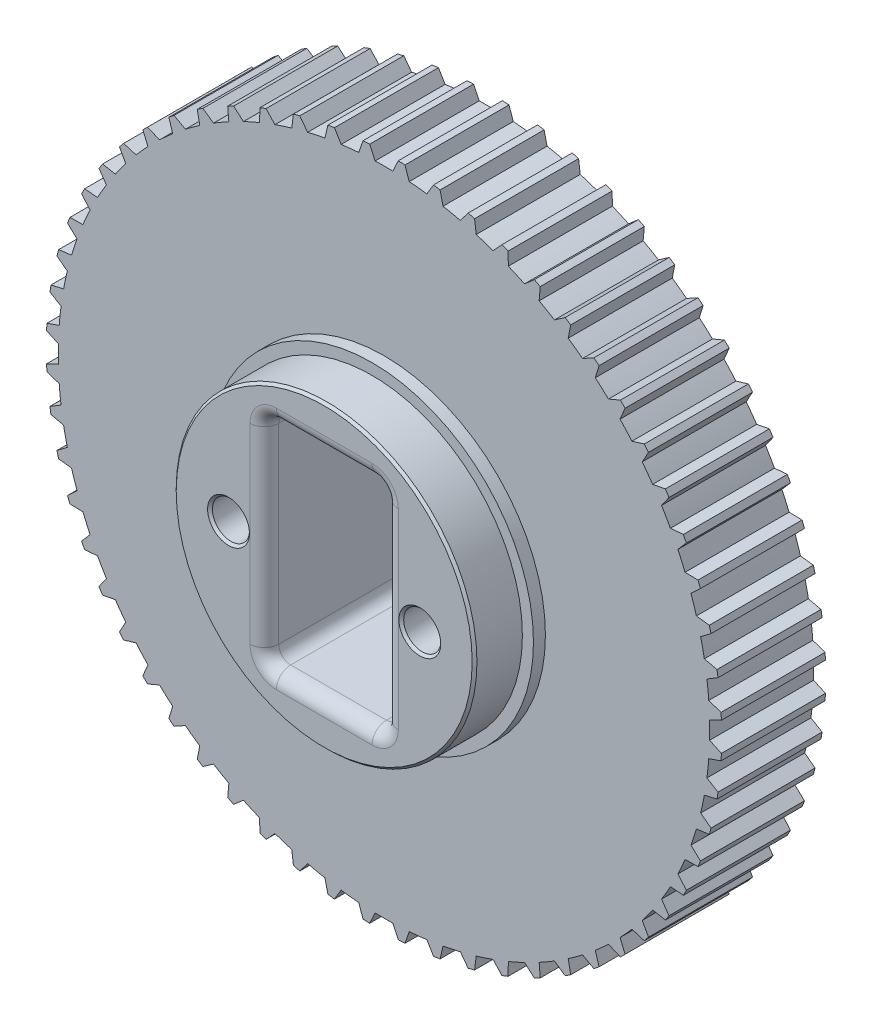
SolidWorks part; units mm, degrees
material "PMMA"
ref_plane "Ebene vorne" through (0, 0, 0) normal (0, 0, 1) x (1, 0, 0)
ref_plane "Ebene oben" through (0, 0, 0) normal (0, 1, 0) x (1, 0, 0)
ref_plane "Ebene rechts" through (0, 0, 0) normal (1, 0, 0) x (0, 0, -1)
ref_axis "Achse1" through (0, 0, 51.6593) along (0, 0, -1)
sketch "Skizze1" plane through (0, 0, 0) normal (1, 0, 0) x (0, 0, -1)
  line L0 (0, 47.6717) -> (0, -53.1541) construction
  line L1 (-46.5152, 0) -> (56.3665, 0) construction
  line L2 (-4.35, 28.24) -> (4.35, 28.24)
  line L3 (4.35, 28.24) -> (4.35, 12.575)
  line L4 (4.35, 12.575) -> (9.35, 12.575)
  line L5 (9.35, 12.575) -> (9.35, 0)
  line L6 (9.35, 0) -> (-9.35, 0)
  line L7 (-9.35, 12.575) -> (-9.35, 0)
  line L8 (-4.35, 12.575) -> (-9.35, 12.575)
  line L9 (-4.35, 28.24) -> (-4.35, 12.575)
  point P12 (0, 0)
  point P15 (0, 28.24)
  dimension "D1" = 9.35
  dimension "D2" = 25.15
  dimension "D3" = 56.48
  dimension "D4" = 8.7
revolve "Rotation1" add sketch "Skizze1" angle 360 about L1
sketch "Skizze2" plane through (0, 0, 0) normal (0, 0, 1) x (1, 0, 0)
  line L0 (0, 30.4501) -> (0, -26.4561) construction
  line L1 (-21.1101, 0) -> (22.7837, 0) construction
  line L2 (-1.2, 28.2145) -> (-0.7409, 27.2299)
  line L3 (1.2, 28.2145) -> (0.7409, 27.2299)
  circle A0 centre (0, 0) radius 27.24 construction
  circle A1 centre (0, 0) radius 28.24 construction
  circle A2 centre (0, 0) radius 28.24 construction
  arc A3 (-1.2, 28.2145) -> (1.2, 28.2145) centre (0, 0) cw
  arc A4 (-0.7409, 27.2299) -> (0.7409, 27.2299) centre (0, 0) cw
  dimension "D1" = 56.48
  dimension "D2" = 54.48
  dimension "D6" = 1
  dimension "D3" = 50
  dimension "D4" = 2.4
  dimension "D5" = 1.4818
extrude "Schnitt-Linear austragen1" cut sketch "Skizze2" against normal through all and the other way through all
pattern_circular "Kreismuster1" count 60 over 360 about axis through (0, 0, 51.6593) along (0, 0, -1) of "Schnitt-Linear austragen1"
sketch "Skizze3" plane through (0, 0, 0) normal (1, 0, 0) x (0, 0, -1)
  line L0 (4.35, 13) -> (4.35, 14.5)
  line L1 (4.35, 14.5) -> (3.85, 14.5)
  line L2 (3.85, 14.5) -> (3.85, 14.25)
  line L3 (3.85, 14.25) -> (3.1964, 13.5964)
  line L4 (3.05, 13.2429) -> (3.05, 13)
  line L5 (3.05, 13) -> (4.35, 13)
  line L6 (4.35, 27.2299) -> (4.35, 28.2145) construction
  line L7 (0, 19.3181) -> (0, -13.1661) construction
  line L8 (11.0313, 0) -> (-11.7934, 0) construction
  arc A0 (3.05, 13.2429) -> (3.1964, 13.5964) centre (3.55, 13.2429) cw
  dimension "D7" = 0.5
  dimension "D1" = 14.5
  dimension "D2" = 13
  dimension "D3" = 0.5
  dimension "D4" = 14.25
  dimension "D5" = 45
  dimension "D6" = 0.8
revolve "Rotation2" add sketch "Skizze3" angle 360 about L8
sketch "Skizze4" plane through (0, 0, 0) normal (0, 0, 1) x (1, 0, 0)
  line L0 (0, 24.4145) -> (0, -17.917) construction
  line L1 (-17.7015, 0) -> (18.3014, 0) construction
  line L2 (4, 9) -> (-4, 9)
  line L3 (-5, 8) -> (-5, -8)
  line L4 (5, 8) -> (5, -8)
  line L5 (4, -9) -> (-4, -9)
  arc A0 (-5, 8) -> (-4, 9) centre (-4, 8) cw
  arc A1 (5, 8) -> (4, 9) centre (4, 8) ccw
  arc A2 (5, -8) -> (4, -9) centre (4, -8) cw
  arc A3 (-5, -8) -> (-4, -9) centre (-4, -8) ccw
  circle A4 centre (-8, 0) radius 1.55
  circle A5 centre (8, 0) radius 1.55
  point P13 (-5, 0)
  point P14 (0, 9)
  point P20 (0, -9)
  point P21 (5, 0)
  dimension "D1" = 1
  dimension "D4" = 3.1
  dimension "D2" = 18
  dimension "D3" = 10
  dimension "D5" = 16
extrude "Schnitt-Linear austragen2" cut sketch "Skizze4" against normal through all and the other way through all
fillet "Verrundung1" radius 1.2 16 edges at (-4.7071, 8.7071, -9.35) (0, 9, -9.35) (4.7071, 8.7071, -9.35) (5, 0, -9.35) (4.7071, -8.7071, -9.35) (0, -9, -9.35) (-4.7071, -8.7071, -9.35) (-4.7071, 8.7071, 9.35) (0, 9, 9.35) (4.7071, 8.7071, 9.35) (5, 0, 9.35) (4.7071, -8.7071, 9.35) (0, -9, 9.35) (-4.7071, -8.7071, 9.35) (-5, 0, -9.35) (-5, 0, 9.35)
chamfer "Fase1" distance 0.2 angle 45 6 edges at (-6.45, 0, -9.35) (6.45, 0, -9.35) (6.45, 0, 9.35) (-6.45, 0, 9.35) (12.575, 0, -9.35) (12.575, 0, 9.35)
sketch "Sketch1" plane through (0, 0, -4.35) normal (0, 0, -1) x (-1, 0, 0)
  circle A0 centre (0, 0) radius 13.5
  circle A1 centre (0, 0) radius 12.575 construction
  circle A2 centre (0, 0) radius 12.575
  dimension "D1" = 27
sketch "Sketch2" plane through (0, 0, 4.35) normal (0, 0, 1) x (1, 0, 0)
  circle A0 centre (0, 0) radius 12.575 construction
  circle A1 centre (0, 0) radius 12.575
  circle A2 centre (0, 0) radius 13.5
  dimension "D1" = 27
extrude "Boss-Extrude2" add sketch "Sketch2" along normal blind 1
sketch "Sketch3" plane through (0, 0, -4.35) normal (0, 0, -1) x (-1, 0, 0)
  circle A1 centre (0, 0) radius 13.5
  circle A2 centre (0, 0) radius 13.5
  circle A3 centre (0, 0) radius 12.575
  circle A4 centre (0, 0) radius 12.575
  dimension "D1" = 0
  dimension "D2" = 0
extrude "Boss-Extrude3" add sketch "Sketch3" along normal blind 2
